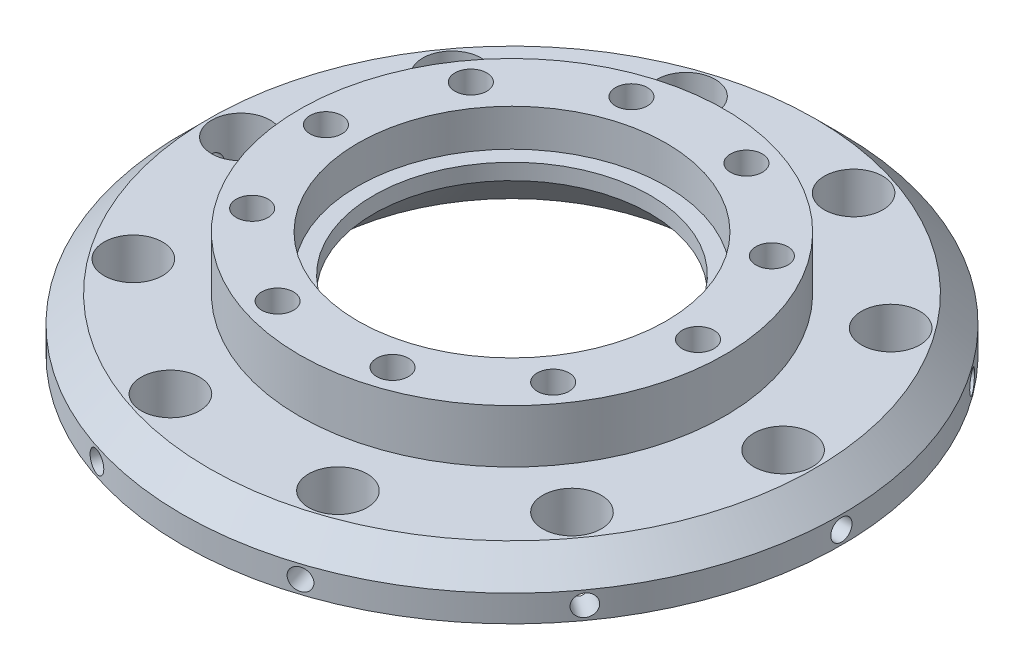
SolidWorks part; units mm, degrees
ref_plane "Front Plane" through (0, 0, 0) normal (0, 0, 1) x (1, 0, 0)
ref_plane "Top Plane" through (0, 0, 0) normal (0, 1, 0) x (1, 0, 0)
ref_plane "Right Plane" through (0, 0, 0) normal (1, 0, 0) x (0, 0, -1)
sketch "Sketch1" plane through (0, 0, 0) normal (0, 1, 0) x (1, 0, 0)
  line L0 (29, 0) -> (41, 0)
  circle A0 centre (0, 0) radius 51
  circle A1 centre (51, 0) radius 5.5
  circle A2 centre (41.2599, -29.977) radius 5.5
  circle A3 centre (15.7599, -48.5039) radius 5.5
  circle A4 centre (-15.7599, -48.5039) radius 5.5
  circle A5 centre (-41.2599, -29.977) radius 5.5
  circle A6 centre (-51, 0) radius 5.5
  circle A7 centre (-41.2599, 29.977) radius 5.5
  circle A8 centre (-15.7599, 48.5039) radius 5.5
  circle A9 centre (15.7599, 48.5039) radius 5.5
  circle A10 centre (41.2599, 29.977) radius 5.5
  circle A11 centre (0, 0) radius 41
  circle A12 centre (0, 0) radius 29
  circle A13 centre (35, 0) radius 3
  circle A14 centre (28.3156, -20.5725) radius 3
  circle A15 centre (10.8156, -33.287) radius 3
  circle A16 centre (-10.8156, -33.287) radius 3
  circle A17 centre (-28.3156, -20.5725) radius 3
  circle A18 centre (-35, 0) radius 3
  circle A19 centre (-28.3156, 20.5725) radius 3
  circle A20 centre (-10.8156, 33.287) radius 3
  circle A21 centre (10.8156, 33.287) radius 3
  circle A22 centre (28.3156, 20.5725) radius 3
  circle A23 centre (0, 0) radius 62
  point P25 (0, 0)
  point P50 (0, 0)
  dimension "D1" = 10
  dimension "D2" = 10
extrude "Boss-Extrude1" add sketch "Sketch1" along normal blind 10 contours A23 A10 A0 A1 A2 A3 A4 A5 A6 A7 A8 A9 | A10 A0 A9 A8 A7 A6 A5 A4 A3 A2 A1 A11 | A13 A11 A12 A22 A21 A20 A19 A18 A17 A16 A15 A14 | A15 | A16 | A17 | A20 | A22 | A21 | A13 | A14 | A18 | A19 region at (-39.8403, 0, 0) region at (44.0617, 0, 0) region at (-60.2464, 0, 0)
sketch "Sketch2" plane through (0, 0, 0) normal (0, 1, 0) x (1, 0, 0)
  circle A0 centre (0, 0) radius 51
  circle A1 centre (51, 0) radius 5.5
  circle A2 centre (41.2599, -29.977) radius 5.5
  circle A3 centre (15.7599, -48.5039) radius 5.5
  circle A4 centre (-15.7599, -48.5039) radius 5.5
  circle A5 centre (-41.2599, -29.977) radius 5.5
  circle A6 centre (-51, 0) radius 5.5
  circle A7 centre (-41.2599, 29.977) radius 5.5
  circle A8 centre (-15.7599, 48.5039) radius 5.5
  circle A9 centre (15.7599, 48.5039) radius 5.5
  circle A10 centre (41.2599, 29.977) radius 5.5
  circle A11 centre (0, 0) radius 40
  circle A12 centre (0, 0) radius 29
  circle A13 centre (35, 0) radius 3
  circle A14 centre (28.3156, -20.5725) radius 3
  circle A15 centre (10.8156, -33.287) radius 3
  circle A16 centre (-10.8156, -33.287) radius 3
  circle A17 centre (-28.3156, -20.5725) radius 3
  circle A18 centre (-35, 0) radius 3
  circle A19 centre (-28.3156, 20.5725) radius 3
  circle A20 centre (-10.8156, 33.287) radius 3
  circle A21 centre (10.8156, 33.287) radius 3
  circle A22 centre (28.3156, 20.5725) radius 3
  circle A23 centre (0, 0) radius 62
  point P25 (0, 0)
  point P50 (0, 0)
  dimension "D1" = 10
  dimension "D2" = 10
extrude "Boss-Extrude2" add sketch "Sketch2" along normal blind 20 contours A13 A11 A12 A22 A21 A20 A19 A18 A17 A16 A15 A14 region at (-38.8686, 0, 0)
sketch "Sketch3" plane through (0, 20, 0) normal (0, 1, 0) x (1, 0, 0)
  circle A0 centre (-28.3156, -20.5725) radius 3
  circle A1 centre (-35, 0) radius 3
  circle A2 centre (-28.3156, 20.5725) radius 3
  circle A3 centre (-10.8156, 33.287) radius 3
  circle A4 centre (10.8156, 33.287) radius 3
  circle A5 centre (28.3156, 20.5725) radius 3
  circle A6 centre (35, 0) radius 3
  circle A7 centre (28.3156, -20.5725) radius 3
  circle A8 centre (10.8156, -33.287) radius 3
  circle A9 centre (-10.8156, -33.287) radius 3
  point P23 (0, 0)
  dimension "D1" = 10
extrude "Boss-Extrude3" add sketch "Sketch3" against normal blind 5 from offset 5 offset against normal yes
chamfer "Chamfer2" distance 5 angle 45 1 edges at (0, 10, 62)
sketch "Sketch4" plane through (0, 0, 0) normal (1, 0, 0) x (0, 0, -1)
  line L0 (0, 0) -> (0, 5)
  line L1 (-62, 5) -> (62, 5) construction
  circle A0 centre (0, 2.5) radius 2
extrude "Cut-Extrude1" cut sketch "Sketch4" along normal blind 15 from offset 51 contours L0 A0 | L0 A0 region at (0, 2.5, 0.8488) region at (0, 2.5, -0.8488)
pattern_circular "CirPattern1" count 10 over 360 about axis through (0, 10, 0) along (0, 1, 0) of "Cut-Extrude1"
chamfer "Chamfer3" distance 1 angle 45 10 edges at (41.2599, 0, 35.477) (51, 0, 5.5) (41.2599, 0, -24.477) (15.7599, 0, -43.0039) (-15.7599, 0, -43.0039) (-41.2599, 0, -24.477) (-51, 0, 5.5) (-41.2599, 0, 35.477) (-15.7599, 0, 54.0039) (15.7599, 0, 54.0039)
sketch "Sketch6" plane through (0, 0, 0) normal (0, -1, 0) x (1, 0, 0)
  circle A0 centre (0, 0) radius 29
  circle A1 centre (0, 0) radius 26
extrude "Boss-Extrude4" add sketch "Sketch6" against normal blind 13
chamfer "Chamfer4" distance 10 angle 45 1 edges at (0, 0, -26)
